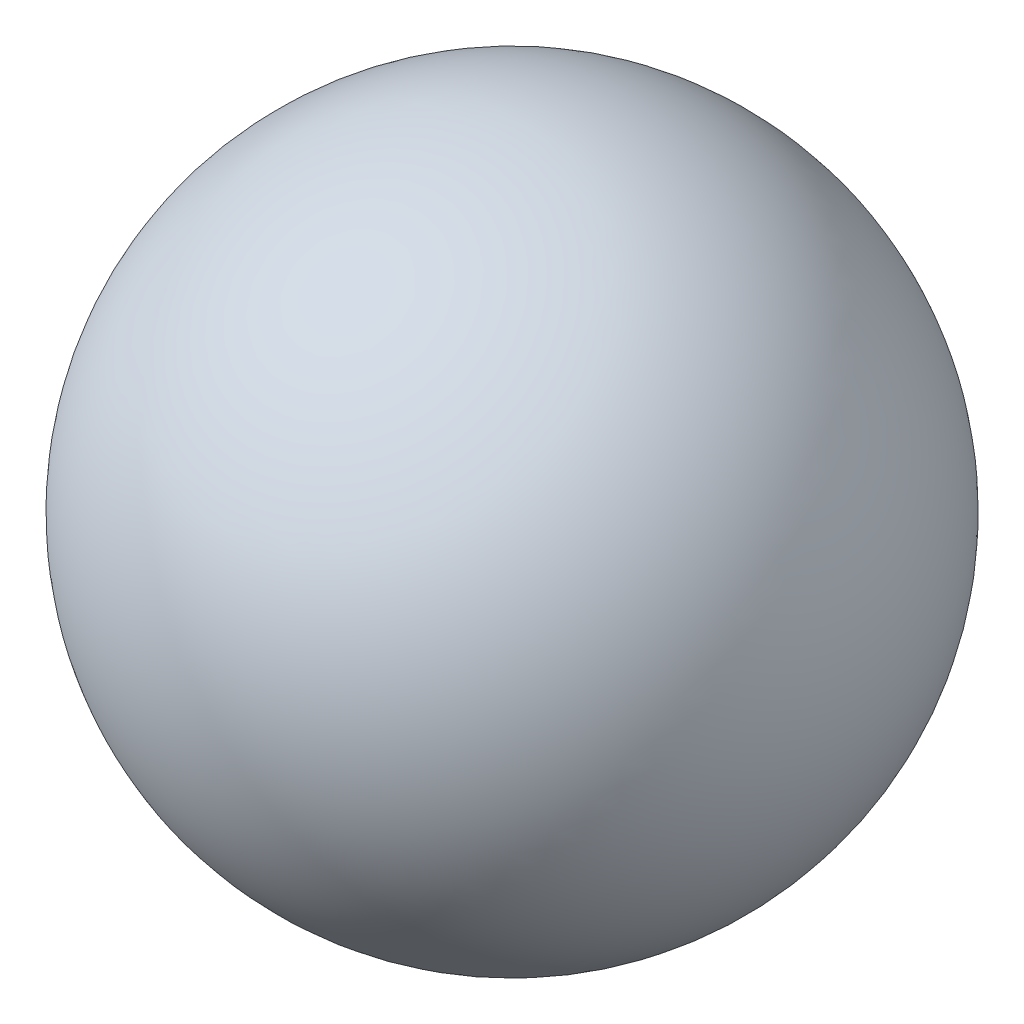
SolidWorks part; units mm, degrees
material "Nylon 6/10"
ref_plane "Front Plane" through (0, 0, 0) normal (0, 0, 1) x (1, 0, 0)
ref_plane "Top Plane" through (0, 0, 0) normal (0, 1, 0) x (1, 0, 0)
ref_plane "Right Plane" through (0, 0, 0) normal (1, 0, 0) x (0, 0, -1)
sketch "Sketch2" plane through (0, 0, 0) normal (0, 1, 0) x (1, 0, 0)
  point P0 (0, 0)
sketch "Sketch1" plane through (0, 0, 0) normal (0, 1, 0) x (1, 0, 0)
  line L0 (0, -717.3915) -> (0, 35152.182) construction
  line L1 (0, -3) -> (0, 3)
  arc A0 (0, -3) -> (0, 3) centre (0, 0) ccw
  point P7 (0, 0)
  dimension "D1" = 3
revolve "Revolve2" add sketch "Sketch1" angle 360 about L0
ref_axis "Axis1" through (0, 0, 717.3915) along (0, 0, -1)
